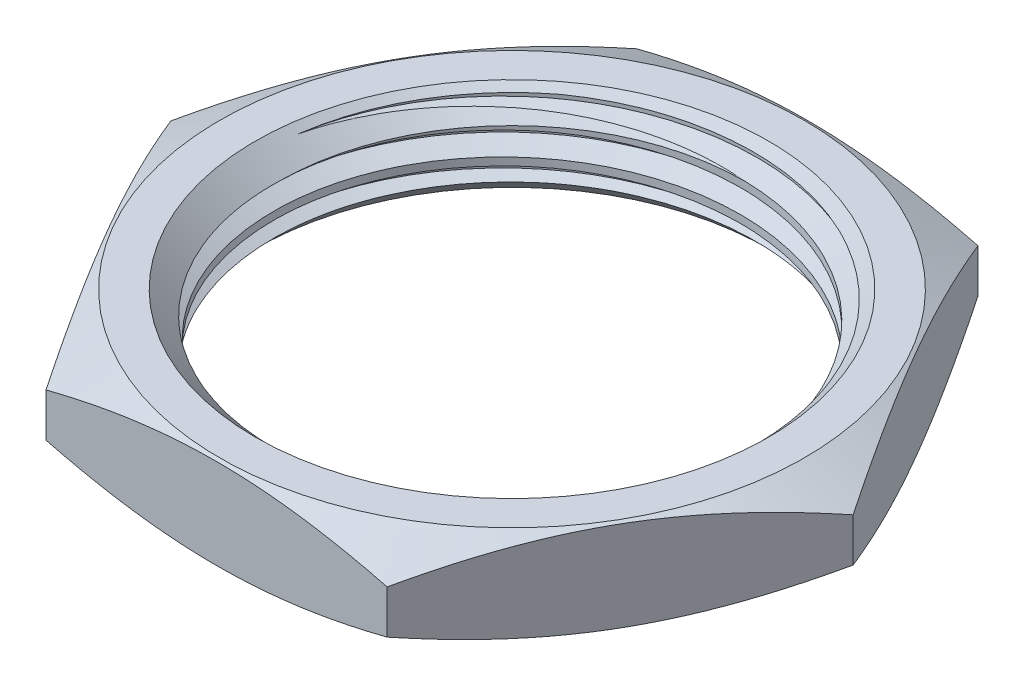
SolidWorks part; units mm, degrees
material "AISI Тип 316L нержавеющая сталь"
ref_plane "Спереди" through (0, 0, 0) normal (0, 0, 1) x (1, 0, 0)
ref_plane "Сверху" through (0, 0, 0) normal (0, 1, 0) x (1, 0, 0)
ref_plane "Справа" through (0, 0, 0) normal (1, 0, 0) x (0, 0, -1)
sketch "Эскиз1" plane through (0, 0, 0) normal (0, 1, 0) x (1, 0, 0)
  line L1 (10.9697, 0) -> (5.4848, 9.5)
  line L2 (5.4848, 9.5) -> (-5.4848, 9.5)
  line L3 (-5.4848, 9.5) -> (-10.9697, 0)
  line L4 (-10.9697, 0) -> (-5.4848, -9.5)
  line L5 (-5.4848, -9.5) -> (5.4848, -9.5)
  line L6 (5.4848, -9.5) -> (10.9697, 0)
  circle A0 centre (0, 0) radius 9.5 construction
  circle A1 centre (0, 0) radius 7.5
  dimension "D1" = 19
extrude "Бобышка-Вытянуть1" add sketch "Эскиз1" along normal blind 3
chamfer "Фаска1" distance 0.75 angle 45 1 edges at (0, 3, 7.5)
chamfer "Фаска3" distance 0.75 angle 45 1 edges at (0, 0, 7.5)
sketch "Эскиз3" plane through (0, 3, 0) normal (0, 1, 0) x (1, 0, 0)
  circle A0 centre (0, 0) radius 9.4
  dimension "D1" = 18.8
sketch "Эскиз5" plane through (0, 0, 0) normal (0, 0, 1) x (1, 0, 0)
  line L0 (-9.4, 3) -> (-10.9697, 3)
  line L1 (-5.4848, 3) -> (-10.9697, 3) construction
  line L2 (9.4, 3) -> (-9.4, 3) construction
  line L3 (-10.9697, 3) -> (-10.9697, 2.2)
  line L4 (-10.9697, 3) -> (-10.9697, 0) construction
  line L5 (-10.9697, 2.2) -> (-9.4, 3)
  line L6 (-10.9697, 0) -> (-10.9697, 0.8)
  line L7 (-10.9697, 0.8) -> (-9.4, 0)
  line L8 (-5.4848, 0) -> (-10.9697, 0) construction
  line L9 (-9.4, 0) -> (-10.9697, 0)
  line L10 (0, 0) -> (0, 3) construction
revolve "Вырез-Повернуть1" cut sketch "Эскиз5" angle 360 about L10
thread "Резьба1" pitch 1 method cut profile "Профиль резьбы1" start angle 0, offset 2, length 0, pitch 1, diameter 15
ref_plane "Плоскость2" through (-7.5, 4.25, 0) normal (0, 0, 1) x (-1, 0, 0)
sketch "Профиль резьбы1" plane through (-7.5, 4.25, 0) normal (0, 0, 1) x (-1, 0, 0)
  line L0 (0, 0) -> (0, 1) construction
  line L1 (0, 0) -> (0.5413, 0.3125)
  line L2 (0.5413, 0.3125) -> (0.5413, 0.4375)
  line L3 (0.5413, 0.4375) -> (0, 0.75)
  line L4 (0.5413, 0.375) -> (0, 0.375) construction
  line L11 (0, 0) -> (0, 0.75)
  point P2 (0, 0)
  dimension "Pitch" = 1
  dimension "Profile_Angle" = 60
  dimension "Profile_Land" = 0.125
  dimension "Profile_Height" = 0.5413
